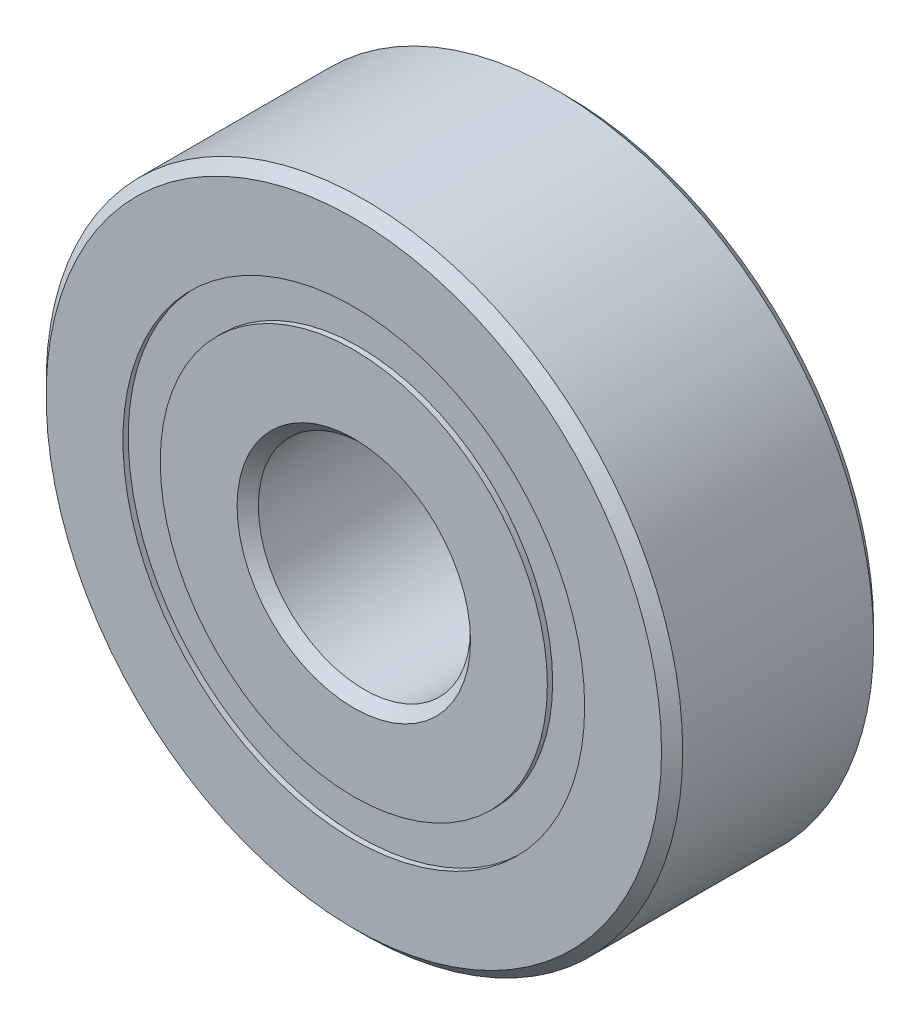
SolidWorks part; units mm, degrees
ref_plane "Front Plane" through (0, 0, 0) normal (0, 0, 1) x (1, 0, 0)
ref_plane "Top Plane" through (0, 0, 0) normal (0, 1, 0) x (1, 0, 0)
ref_plane "Right Plane" through (0, 0, 0) normal (1, 0, 0) x (0, 0, -1)
sketch "Sketch1" plane through (0, 0, 0) normal (1, 0, 0) x (0, 0, -1)
  line L0 (-2, 0) -> (2, 0) construction
  line L1 (0, 6) -> (0, -6) construction
  line L2 (1.8, 6) -> (-1.8, 6)
  line L3 (-1.8, 6) -> (-2, 5.8)
  line L4 (-2, 5.8) -> (-2, 4.3516)
  line L5 (-2, 4.3516) -> (-0.8889, 4.3516)
  line L6 (2, 4.3516) -> (0.8889, 4.3516)
  line L7 (2, 5.8) -> (2, 4.3516)
  line L8 (1.8, 6) -> (2, 5.8)
  line L9 (0, 6) -> (0, 4) construction
  line L10 (0, 4) -> (0, 2) construction
  arc A0 (-0.8889, 4.3516) -> (0.8889, 4.3516) centre (0, 4) cw
  point P14 (0, 2)
  dimension "Width" = 4
  dimension "OD" = 12
  dimension "D1" = 45
  dimension "D2" = 0.2
  dimension "Shaft Dia" = 4
  dimension "D3" = 1.7778
  dimension "D4" = 0.3516
revolve "Revolve1" add sketch "Sketch1" angle 360 about L0
sketch "Sketch3" plane through (0, 0, 0) normal (1, 0, 0) x (0, 0, -1)
  line L0 (-2, 3.6484) -> (-0.8889, 3.6484)
  line L1 (0, 6) -> (0, -6) construction
  line L2 (-2, 5.8) -> (-2, 4.3516) construction
  line L3 (-2, 3.6484) -> (-2, 2.2)
  line L4 (-1.8, 6) -> (-2, 5.8) construction
  line L5 (-2, 2.2) -> (-1.8, 2)
  line L6 (-1.8, 2) -> (1.8, 2)
  line L7 (1.8, 6) -> (1.8, -6) construction
  line L8 (1.8, 2) -> (2, 2.2)
  line L9 (2, -5.8) -> (2, 5.8) construction
  line L10 (2, 2.2) -> (2, 3.6484)
  line L11 (2, 3.6484) -> (0.8889, 3.6484)
  line L13 (1.8, 6) -> (2, 5.8) construction
  arc A0 (0.8889, 4.3516) -> (-0.8889, 4.3516) centre (0, 4) ccw construction
  arc A1 (0.8889, 3.6484) -> (-0.8889, 3.6484) centre (0, 4) cw
revolve "Revolve3" add sketch "Sketch3" angle 360 about L0
sketch "Sketch4" plane through (0, 0, 0) normal (1, 0, 0) x (0, 0, -1)
  line L0 (-0.9559, 4) -> (0.9559, 4)
  arc A2 (-0.9559, 4) -> (0.9559, 4) centre (0, 4) cw
  arc A3 (0.8889, 4.3516) -> (-0.8889, 4.3516) centre (0, 4) ccw construction
revolve "Revolve4" add sketch "Sketch4" angle 360 about L0
ref_axis "Axis1" through (0, 0, -2) along (0, 0, 1)
pattern_circular "CirPattern1" count 12 every 30 about axis through (0, 0, -2) along (0, 0, 1) of bodies 104
sketch "Sketch5" plane through (0, 0, 0) normal (1, 0, 0) x (0, 0, -1)
  line L0 (-2, 4.3516) -> (-0.8889, 4.3516) construction
  line L1 (-1.9, 4.3516) -> (-0.9559, 4.3516)
  line L2 (-1.9, 4.3516) -> (-1.9, 3.6484)
  line L3 (-1.9, 3.6484) -> (-0.9559, 3.6484)
  line L4 (-0.9559, 4.3516) -> (-0.9559, 3.6484)
  line L5 (-2, 3.6484) -> (-0.8889, 3.6484) construction
  line L6 (2, 4.3516) -> (0.8889, 4.3516) construction
  line L7 (1.9, 4.3516) -> (0.9559, 4.3516)
  line L8 (1.9, 4.3516) -> (1.9, 3.6484)
  line L9 (1.9, 3.6484) -> (0.9559, 3.6484)
  line L10 (0.9559, 4.3516) -> (0.9559, 3.6484)
  line L11 (2, 3.6484) -> (0.8889, 3.6484) construction
  line L12 (-1.8, 6) -> (-2, 5.8) construction
  point P18 (-1.9, 5.9)
revolve "Revolve5" add sketch "Sketch5" angle 360 about L0
sketch "Sketch6" plane through (0, 0, 0) normal (1, 0, 0) x (0, 0, -1)
  line L0 (2, 0) -> (-2, 0) construction
  line L1 (2, 4.3516) -> (0.9, 4.3516)
  line L2 (2, 4.3516) -> (2, 9.5)
  line L3 (2, 9.5) -> (0.9, 9.5)
  line L4 (0.9, 4.3516) -> (0.9, 9.5)
  dimension "Th" = 1.1
  dimension "Flange OD" = 19
revolve "Revolve6" [suppressed] add sketch "Sketch6" angle 360 about L0
equation "\"D2@Sketch1\" = \"Width@Sketch1\"*.05"
equation "\"D3@Sketch1\" = \"Width@Sketch1\"/2.25"
equation "\"D4@Sketch1\" = (((\"OD@Sketch1\"-\"Width@Sketch1\")/2)/3.25)/3.5"
equation "\"D2@CirPattern1\" = 360/\"Balls@CirPattern1\""
